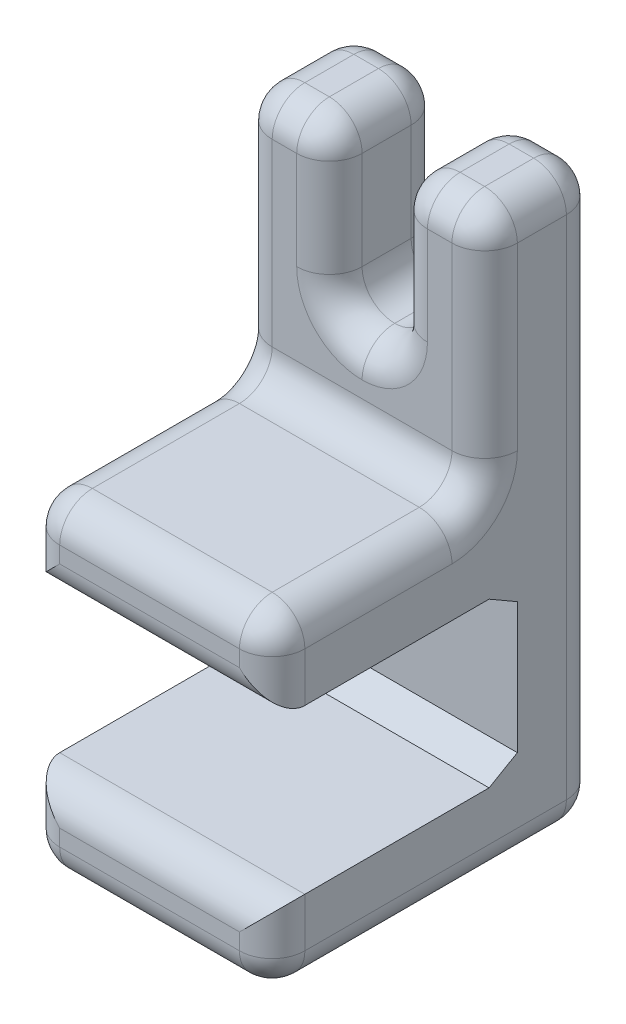
SolidWorks part; units mm, degrees
ref_plane "Front Plane" through (0, 0, 0) normal (0, 0, 1) x (1, 0, 0)
ref_plane "Top Plane" through (0, 0, 0) normal (0, 1, 0) x (1, 0, 0)
ref_plane "Right Plane" through (0, 0, 0) normal (1, 0, 0) x (0, 0, -1)
sketch "Sketch1" plane through (0, 0, 0) normal (0, 0, 1) x (1, 0, 0)
  line L1 (0, 0) -> (-15, 0)
  line L2 (0, 0) -> (0, 35)
  line L3 (0, 35) -> (-15, 35)
  line L4 (-15, 0) -> (-15, 35)
  dimension "D1" = 35
  dimension "D2" = 15
extrude "Boss-Extrude1" add sketch "Sketch1" along normal blind 20
sketch "Sketch2" plane through (0, 0, 0) normal (1, 0, 0) x (0, 0, -1)
  line L0 (-20, 0) -> (-20, 35) construction
  line L1 (-20, 15) -> (-5, 15)
  line L2 (-20, 15) -> (-20, 5)
  line L3 (-20, 5) -> (-5, 5)
  line L4 (-5, 15) -> (-5, 5)
  line L5 (-20, 0) -> (0, 0) construction
  line L6 (0, 0) -> (0, 35) construction
  dimension "D1" = 5
  dimension "D2" = 5
  dimension "10,5" = 10
extrude "Cut-Extrude1" cut sketch "Sketch2" against normal through all
sketch "Sketch4" plane through (-15, 0, 0) normal (-1, 0, 0) x (0, 0, 1)
  line L0 (5, 15) -> (20, 15) construction
  line L1 (20, 20) -> (7, 20)
  line L2 (20, 20) -> (20, 35)
  line L3 (20, 35) -> (7, 35)
  line L4 (7, 20) -> (7, 35)
  point P4 (0, 0)
  dimension "D1" = 5
  dimension "D2" = 13
extrude "Cut-Extrude3" cut sketch "Sketch4" against normal through all
sketch "Sketch5" plane through (0, 0, 0) normal (0, 0, -1) x (-1, 0, 0)
  line L1 (5.5, 35) -> (9.5, 35)
  line L2 (5.5, 35) -> (5.5, 25)
  line L3 (5.5, 25) -> (9.5, 25)
  line L4 (9.5, 35) -> (9.5, 25)
  line L6 (5.5, 25) -> (9.5, 25) construction
  line L9 (0, 35) -> (15, 35) construction
  line L10 (0, 35) -> (15, 35) construction
  line L11 (0, 20) -> (15, 20) construction
  point P10 (7.5, 35)
  point P11 (7.5, 35)
  dimension "D1" = 4
  dimension "D2" = 5
extrude "Cut-Extrude4" cut sketch "Sketch5" against normal up to next and the other way through all
fillet "Fillet2" radius 2 34 edges at (-9.5, 35, 3.5) (-5.5, 35, 3.5) (-5.5, 25, 3.5) (-9.5, 25, 3.5) (-2.75, 35, 7) (-12.25, 35, 7) (-9.5, 30, 7) (-7.5, 25, 7) (-5.5, 30, 7) (-7.5, 20, 7) (-15, 35, 3.5) (-15, 27.5, 7) (-15, 20, 13.5) (-15, 2.5, 20) (-7.5, 5, 20) (-7.5, 15, 20) (-15, 17.5, 20) (-7.5, 20, 20) (0, 35, 3.5) (0, 2.5, 20) (0, 17.5, 20) (0, 20, 13.5) (0, 27.5, 7) (-15, 0, 10) (-7.5, 0, 20) (0, 0, 10) (-7.5, 25, 0) (-9.5, 30, 0) (-12.25, 35, 0) (-15, 17.5, 0) (-7.5, 0, 0) (0, 17.5, 0) (-2.75, 35, 0) (-5.5, 30, 0)
chamfer "Chamfer1" distance 1 angle 60 2 edges at (-7.5, 5, 5) (-7.5, 15, 5) first distance on face at (-7.5, 10, 5)
